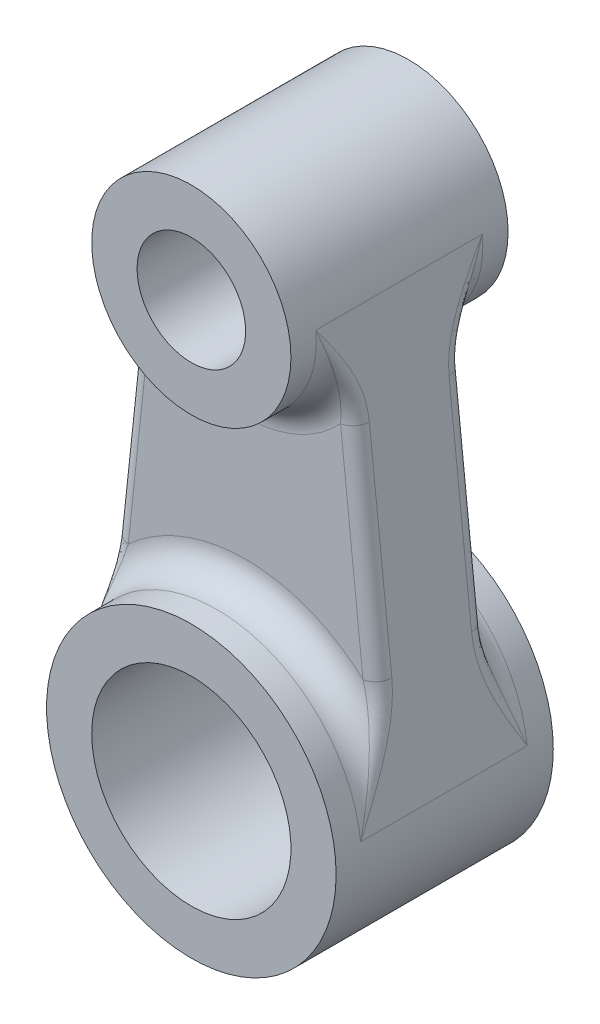
SolidWorks part; units mm, degrees
ref_plane "Front" through (0, 0, 0) normal (0, 0, 1) x (1, 0, 0)
ref_plane "Top" through (0, 0, 0) normal (0, 1, 0) x (1, 0, 0)
ref_plane "Right" through (0, 0, 0) normal (1, 0, 0) x (0, 0, -1)
sketch "Sketch1" plane through (0, 0, 0) normal (0, 0, 1) x (1, 0, 0)
  circle A0 centre (0, 0) radius 12.7
  circle A1 centre (0, 0) radius 8.7376
  circle A2 centre (0, 37.3126) radius 8.7376
  circle A3 centre (0, 37.3126) radius 4.7625
  dimension "D1" = 25.4
  dimension "D2" = 17.4752
  dimension "D4" = 17.4752
  dimension "D5" = 9.525
  dimension "D3" = 37.3126
extrude "Boss-Extrude1" add sketch "Sketch1" along normal mid plane 19.05
sketch "Sketch2" plane through (0, 0, 0) normal (0, 0, 1) x (1, 0, 0)
  line L0 (8.6882, 38.2405) -> (12.6282, 1.3487)
  line L1 (-8.6882, 38.2405) -> (-12.6282, 1.3487)
  circle A0 centre (0, 37.3126) radius 8.7376 construction
  circle A1 centre (0, 0) radius 12.7 construction
  arc A2 (12.6282, 1.3487) -> (-12.6282, 1.3487) centre (0, 0) ccw
  arc A3 (-8.6882, 38.2405) -> (8.6882, 38.2405) centre (0, 37.3126) ccw
extrude "Boss-Extrude2" add sketch "Sketch2" along normal mid plane 9.525
fillet "Fillet1" radius 2.54 4 edges at (0, 12.7, -4.7625) (0, 12.7, 4.7625) (0, 28.575, 4.7625) (0, 28.575, -4.7625)
fillet "Fillet2" radius 1.27 12 edges at (12.1224, 6.0845, -5.3942) (9.1848, 33.5909, -5.162) (12.1224, 6.0845, 5.3942) (9.1848, 33.5909, 5.162) (-9.1848, 33.5909, 5.162) (-12.1224, 6.0845, 5.3942) (-9.1848, 33.5909, -5.162) (-12.1224, 6.0845, -5.3942) (10.5895, 20.438, -4.7625) (10.5895, 20.438, 4.7625) (-10.5895, 20.438, 4.7625) (-10.5895, 20.438, -4.7625)
